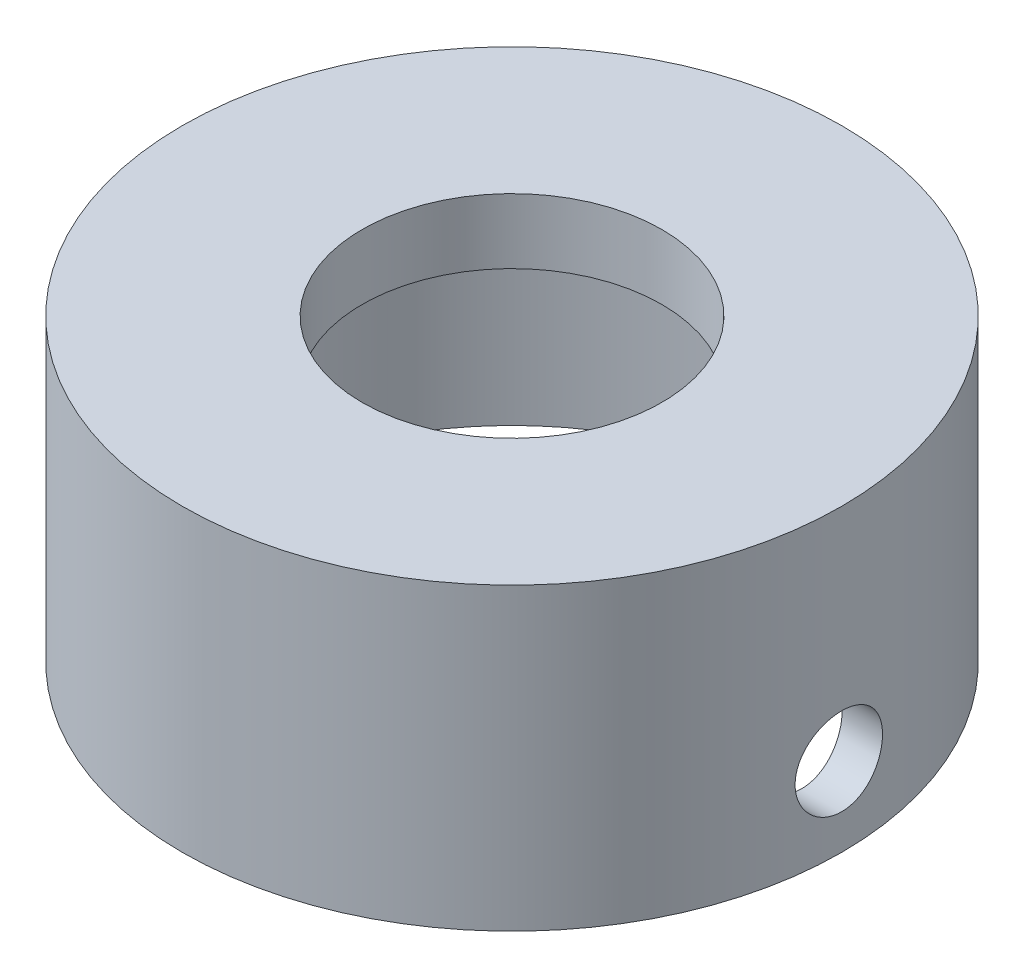
SolidWorks part; units mm, degrees
ref_plane "Front Plane" through (0, 0, 0) normal (0, 0, 1) x (1, 0, 0)
ref_plane "Top Plane" through (0, 0, 0) normal (0, 1, 0) x (1, 0, 0)
ref_plane "Right Plane" through (0, 0, 0) normal (1, 0, 0) x (0, 0, -1)
sketch "Sketch1" plane through (0, 0, 0) normal (0, 1, 0) x (1, 0, 0)
  circle A0 centre (0, 0) radius 20.955
  dimension "D2" = 41.91
extrude "Boss-Extrude1" add sketch "Sketch1" against normal blind 19.05
sketch "Sketch2" plane through (0, -19.05, 0) normal (0, -1, 0) x (1, 0, 0)
  circle A0 centre (0, 0) radius 18.415
  dimension "D1" = 36.83
extrude "Cut-Extrude1" cut sketch "Sketch2" against normal blind 13.3985
sketch "Sketch3" plane through (0, 0, 0) normal (0, 1, 0) x (1, 0, 0)
  circle A0 centre (0, 0) radius 9.525
  dimension "D1" = 19.05
extrude "Cut-Extrude2" cut sketch "Sketch3" against normal through all
sketch "Sketch4" plane through (0, -5.6515, 0) normal (0, -1, 0) x (1, 0, 0)
  circle A0 centre (0, 0) radius 15.875
  dimension "D1" = 31.75
extrude "Cut-Extrude3" cut sketch "Sketch4" against normal blind 1.524
sketch "Sketch5" plane through (0, 0, 0) normal (1, 0, 0) x (0, 0, -1)
  line L0 (-15.875, -4.1275) -> (15.875, -4.1275) construction
  circle A0 centre (0, -14.0335) radius 2.7781
  dimension "D1" = 5.5562
  dimension "D2" = 9.906
extrude "Cut-Extrude4" cut sketch "Sketch5" against normal through all and the other way through all
